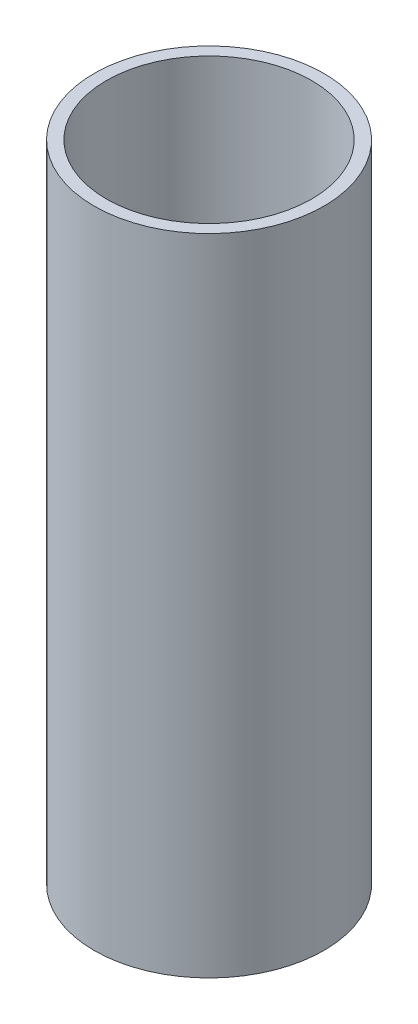
SolidWorks part; units mm, degrees
ref_plane "Front Plane" through (0, 0, 0) normal (0, 0, 1) x (1, 0, 0)
ref_plane "Top Plane" through (0, 0, 0) normal (0, 1, 0) x (1, 0, 0)
ref_plane "Right Plane" through (0, 0, 0) normal (1, 0, 0) x (0, 0, -1)
sketch "Sketch1" plane through (0, 0, 0) normal (0, 1, 0) x (1, 0, 0)
  circle A0 centre (0, 0) radius 50
  dimension "SLEEVE_OD" = 100
extrude "Boss-Extrude1" add sketch "Sketch1" along normal blind 280.5069
sketch "Sketch2" plane through (0, 0, 0) normal (0, 1, 0) x (1, 0, 0)
  circle A0 centre (0, 0) radius 44.665
  dimension "BORE_D" = 89.3299
extrude "Cut-Extrude1" cut sketch "Sketch2" along normal through all
chamfer "Chamfer1" distance 2.1312 angle 62.57 rebuild error yes
